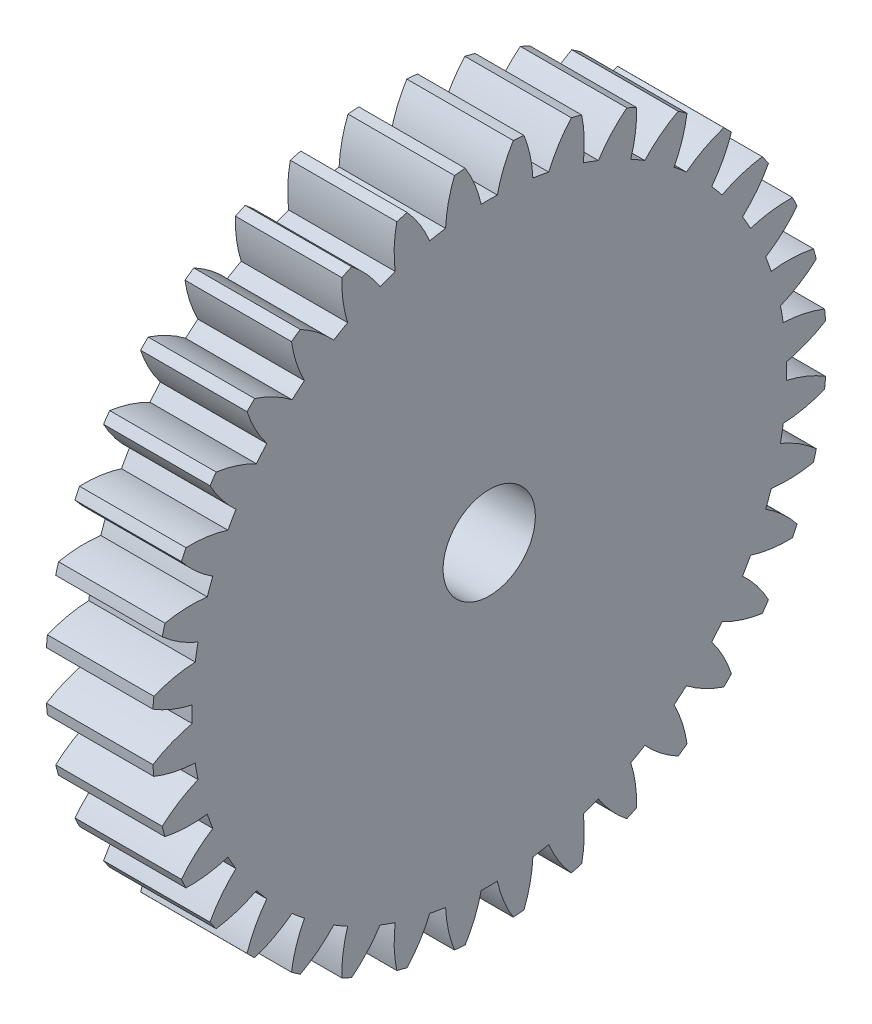
SolidWorks part; units mm, degrees
ref_plane "Plane1" through (0, 0, 0) normal (0, 0, 1) x (1, 0, 0)
ref_plane "Plane2" through (0, 0, 0) normal (0, 1, 0) x (1, 0, 0)
ref_plane "Plane3" through (0, 0, 0) normal (1, 0, 0) x (0, 0, -1)
sketch "HoldingSke" plane through (0, 0, 0) normal (0, 1, 0) x (1, 0, 0)
  line L0 (0, 0) -> (0.809, -0.5878)
  line L1 (-15, 0) -> (100, 0) construction
  line L2 (0, 0) -> (-2.1039, 2.3779)
  line L3 (0, 0) -> (-11.863, 4.5341)
  line L4 (0, 0) -> (6.9867, 5.0761)
  line L5 (0, 0) -> (-46.8476, -17.4728)
  line L6 (0, 0) -> (-4.9738, -3.3558)
  line L7 (-2.1039, 2.3779) -> (8.6586, 51.2059)
  line L8 (-76.2, 54.61) -> (-76.1, 54.61)
  line L9 (-71.009, 38.7566) -> (-53.1078, 45.2721)
  line L10 (-76.2, 71.12) -> (104.1128, 71.12)
  line L11 (0, 0) -> (-6, 0)
  line L12 (-76.2, 101.6) -> (-76.162, 101.6)
  line L13 (24.9733, 27.94) -> (52.9518, 28.4284)
  line L14 (24.9733, 27.94) -> (24.9743, 27.94)
  line L15 (24.9733, 27.94) -> (100.4006, 29.5858)
  line L16 (-63.627, -1) -> (-12.827, -1)
  circle A0 centre (0, 0) radius 0.4
  circle A1 centre (0, 0) radius 16.749
  circle A2 centre (0, 0) radius 37.5
  circle A3 centre (0, 0) radius 0.4
  dimension "Num_teeth" = 36
  dimension "Pitch_radius" = 180.3128
  dimension "Width" = 6
  dimension "Thickness" = 6
sketch "BasProSke" plane through (0, 0, 0) normal (0, 1, 0) x (1, 0, 0)
  line L0 (-10, 0) -> (60, 0) construction
  line L1 (0, 0) -> (0, 19)
  line L2 (0, 0) -> (6, 0)
  line L3 (6, 0) -> (6, 19)
  line L4 (6, 19) -> (0, 19)
  dimension "Thickness" = 6
  dimension "Diameter" = 38
revolve "Base-Revolve" add sketch "BasProSke" angle 360 about L0
sketch "TooCutSke" plane through (0, 0, 0) normal (1, 0, 0) x (0, 0, -1)
  line L1 (0, 0) -> (0, 107) construction
  line L2 (0, 0) -> (-0.8516, 17.9798) construction
  line L3 (0, 0) -> (-3.1351, 35.8344) construction
  line L4 (-0.8516, 17.9798) -> (-1.5676, 17.9172) construction
  arc A0 (0.4547, 16.7428) -> (-0.4547, 16.7428) centre (0, 0) ccw
  arc A1 (1.3689, 18.9761) -> (-1.3689, 18.9761) centre (0, 0) ccw
  circle A2 centre (0, 0) radius 18 construction
  circle A3 centre (0, 0) radius 16.9145 construction
  arc A4 (-0.4547, 16.7428) -> (-1.3689, 18.9761) centre (-7.4808, 15.1702) ccw
  arc A5 (1.3689, 18.9761) -> (0.4547, 16.7428) centre (7.4808, 15.1702) ccw
extrude "ToothCut" cut sketch "TooCutSke" along normal through all
fillet "Breaks" [suppressed] radius 0.02 tangent propagation no
fillet "RootFillets" [suppressed] radius 0.251
pattern_circular "TeethCuts" count 36 over 360 about axis through (-10, 0, 0) along (1, 0, 0) of "ToothCut", "RootFillets", "Breaks"
sketch "HubNeaOneSke" plane through (0, 0, 0) normal (-1, 0, 0) x (0, 0, 1)
  circle A0 centre (0, 0) radius 16.749
  dimension "Diameter" = 33.498
extrude "HubNearOne" [suppressed] add sketch "HubNeaOneSke" along normal blind 44.0001
sketch "HubNeaBotSke" plane through (0, 0, 0) normal (-1, 0, 0) x (0, 0, 1)
  circle A0 centre (0, 0) radius 16.749
  dimension "Diameter" = 33.498
extrude "HubNearBoth" [suppressed] add sketch "HubNeaBotSke" along normal blind 22
ref_plane "FarPln" through (6, 0, 0) normal (1, 0, 0) x (0, 0, -1)
sketch "HubFarSke" plane through (6, 0, 0) normal (1, 0, 0) x (0, 0, -1)
  circle A0 centre (0, 0) radius 16.749
  dimension "Diameter" = 33.498
extrude "HubFar" [suppressed] add sketch "HubFarSke" along normal blind 22
sketch "BorSke" plane through (0, 0, 0) normal (1, 0, 0) x (0, 0, -1)
  circle A0 centre (0, 0) radius 0.4
  dimension "Diameter" = 0.8
extrude "Bore" cut sketch "BorSke" along normal mid plane 100.0001
sketch "KeySke" plane through (0, 0, 0) normal (1, 0, 0) x (0, 0, -1)
  line L0 (-0.05, 0) -> (-0.05, 0.5)
  line L1 (-0.05, 0.5) -> (0.05, 0.5)
  line L2 (0.05, 0.5) -> (0.05, 0)
  line L3 (0, 0) -> (0, 34) construction
  line L4 (-0.05, 0) -> (0.05, 0)
  dimension "Width" = 0.1
extrude "Keyway" [suppressed] cut sketch "KeySke" along normal mid plane 100.0001
pattern_circular "Keyway2" [suppressed] count 2 every 90 about axis through (-10, 0, 0) along (1, 0, 0) reverse direction yes
sketch "Sketch1" plane through (6, 0, 0) normal (1, 0, 0) x (0, 0, -1)
  circle A0 centre (0, 0) radius 2.6
extrude "Cut-Extrude1" cut sketch "Sketch1" against normal through all contours A0
equation "' \"Module@HoldingSke\" = 6.35"
equation "' \"Num_teeth@HoldingSke\" = 12"
equation "' \"Ap@HoldingSke\" =  20"
equation "' \"Ap@HoldingSke\" = 20"
equation "' \"Width@HoldingSke\" = 0.5 * 25.4"
equation "' \"Hub_dia@HoldingSke\"= 1 * 25.4"
equation "' \"Hub_dia@HoldingSke\" = 1 * 25.4"
equation "' \"Overall_len@HoldingSke\" = 1.0 * 25.4"
equation "' \"Bore@HoldingSke\" = 0.75 * 25.4"
equation "' \"T_dim@HoldingSke\" = 0.1 * 25.4"
equation "' \"Width@KeySke\" = 0.25 * 25.4"
equation "' \"Show_teeth@HoldingSke\" = 13"
equation "' \"Backlash@HoldingSke\" = 0.009 * 25.4"
equation "' \"Addendum_fac@HoldingSke\" = 1.0"
equation "' \"Dedendum_fac@HoldingSke\" = 1.25"
equation "' \"Dedendum_add@HoldingSke\" = 0.00005 * 25.4"
equation "' \"Clearance_fac@HoldingSke\" = 0.25"
equation "\"Pitch@HoldingSke\" = 1 / \"Module@HoldingSke\""
equation "\"Overcut_dia@TooCutSke\" = (\"Num_teeth@HoldingSke\" + 2 * \"Addendum_fac@HoldingSke\") / \"Pitch@HoldingSke\" + 0.002 * 25.4"
equation "\"Pitch_dia@TooCutSke\" = \"Num_teeth@HoldingSke\" / \"Pitch@HoldingSke\""
equation "\"Base_dia@TooCutSke\" = \"Num_teeth@HoldingSke\" / \"Pitch@HoldingSke\" * cos((\"Ap@HoldingSke\"  * 3.14159265 / 180))"
equation "\"Root_dia@TooCutSke\" = (\"Num_teeth@HoldingSke\" + 2) / \"Pitch@HoldingSke\" - 2 * (\"Addendum_fac@HoldingSke\" + \"Dedendum_fac@HoldingSke\") / \"Pitch@HoldingSke\" - \"Dedendum_add@HoldingSke\" * 2"
equation "\"Half_ang@TooCutSke\" = 180 / \"Num_teeth@HoldingSke\""
equation "\"Half_CT@TooCutSke\" = \"Num_teeth@HoldingSke\" / \"Pitch@HoldingSke\" * sin((3.14159265 / 2 / \"Num_teeth@HoldingSke\")) / 2 - 7 * \"Backlash@HoldingSke\" / 4"
equation "\"Flank_rad@TooCutSke\" = \"Num_teeth@HoldingSke\" / \"Pitch@HoldingSke\" / 5"
equation "\"Radius@RootFillets\" = \"Clearance_fac@HoldingSke\" / \"Pitch@HoldingSke\" + \"Dedendum_add@HoldingSke\""
equation "\"Break_rad@Breaks\" = 0.02 / \"Pitch@HoldingSke\""
equation "\"Thickness@HoldingSke\" = \"Width@HoldingSke\""
equation "\"OAL@HoldingSke\" = \"Thickness@HoldingSke\""
equation "\"MHD@HoldingSke\" = (\"Num_teeth@HoldingSke\" + 2) / \"Pitch@HoldingSke\" - 2 * (\"Addendum_fac@HoldingSke\" + \"Dedendum_fac@HoldingSke\")  / \"Pitch@HoldingSke\" - \"Dedendum_add@HoldingSke\" * 2"
equation "\"MBD@HoldingSke\" = (\"Num_teeth@HoldingSke\" + 2) / \"Pitch@HoldingSke\" - 2 * (\"Addendum_fac@HoldingSke\" + \"Dedendum_fac@HoldingSke\")  / \"Pitch@HoldingSke\" - \"Dedendum_add@HoldingSke\" * 2 - 0.002 * 25.4"
equation "\"MHD@HoldingSke\" = ((sgn( \"MHD@HoldingSke\" - \"Hub_dia@HoldingSke\" )-1)*( \"MHD@HoldingSke\" - \"Hub_dia@HoldingSke\" ))/-2+ \"Hub_dia@HoldingSke\""
equation "\"MBD@HoldingSke\" = ((sgn( \"MBD@HoldingSke\" - \"Bore@HoldingSke\" )-1)*( \"MBD@HoldingSke\" - \"Bore@HoldingSke\" ))/-2+ \"Bore@HoldingSke\""
equation "\"OAL@HoldingSke\" = ((sgn( \"OAL@HoldingSke\" - \"Overall_len@HoldingSke\" )+1)*( \"OAL@HoldingSke\" - \"Overall_len@HoldingSke\" ))/2 + \"Overall_len@HoldingSke\" + 0.000002 * 25.4"
equation "\"Num_teeth@TeethCuts\" = int( \"Show_teeth@HoldingSke\" ) + 1"
equation "\"Num_teeth@TeethCuts\" = ((sgn( \"Num_teeth@TeethCuts\" - \"Num_teeth@HoldingSke\" )-1)*( \"Num_teeth@TeethCuts\" - \"Num_teeth@HoldingSke\" ))/-2+ \"Num_teeth@HoldingSke\""
equation "\"Num_teeth@TeethCuts\" = ((sgn( \"Num_teeth@TeethCuts\" - 2.0)+1)*( \"Num_teeth@TeethCuts\" - 2.0))/2 +2.0"
equation "\"Angle@TeethCuts\" = 360.0 / \"Num_teeth@HoldingSke\""
equation "\"Diameter@BasProSke\" = (\"Num_teeth@HoldingSke\" + 2 * \"Addendum_fac@HoldingSke\") / \"Pitch@HoldingSke\""
equation "\"Thickness@BasProSke\"  = \"Thickness@HoldingSke\""
equation "' \"Fillet_rad@BasProSke\" =  \"Thickness@HoldingSke\" * 0.05"
equation "' \"Fillet_rad@BasProSke\" = \"Thickness@HoldingSke\" * 0.05"
equation "\"MHD@HoldingSke\" = ((sgn( \"MHD@HoldingSke\" - \"Root_dia@TooCutSke\" )-1)*( \"MHD@HoldingSke\" - \"Root_dia@TooCutSke\" ))/-2+ \"Root_dia@TooCutSke\""
equation "\"Diameter@HubNeaOneSke\" = \"MHD@HoldingSke\""
equation "\"Length@HubNearOne\" = \"OAL@HoldingSke\" - \"Thickness@BasProSke\""
equation "\"Diameter@HubNeaBotSke\" = \"MHD@HoldingSke\""
equation "\"Length@HubNearBoth\" = ( \"OAL@HoldingSke\" - \"Thickness@BasProSke\" ) / 2.0"
equation "\"Thickness@FarPln\" = \"Thickness@BasProSke\""
equation "\"Diameter@HubFarSke\" = \"MHD@HoldingSke\""
equation "\"Length@HubFar\" = ( \"OAL@HoldingSke\" - \"Thickness@BasProSke\" ) / 2.0"
equation "\"Diameter@BorSke\" = \"MBD@HoldingSke\""
equation "\"D1@Bore\" = \"OAL@HoldingSke\" * 2.0"
equation "\"D1@Keyway\" = \"OAL@HoldingSke\" * 2.0"
equation "\"Offset@KeySke\" = \"T_dim@HoldingSke\" + \"MBD@HoldingSke\" / 2.0"
